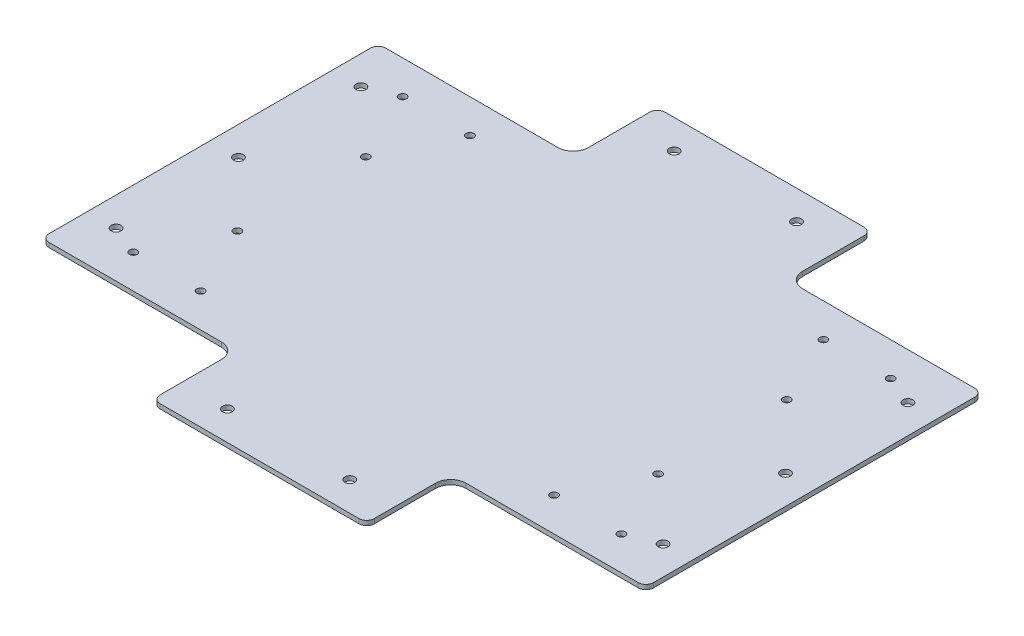
SolidWorks part; units mm, degrees
material "1060 Сплав"
ref_plane "Спереди" through (0, 0, 0) normal (0, 0, 1) x (1, 0, 0)
ref_plane "Сверху" through (0, 0, 0) normal (0, 1, 0) x (1, 0, 0)
ref_plane "Справа" through (0, 0, 0) normal (1, 0, 0) x (0, 0, -1)
sketch "Эскиз1" plane through (0, 0, 0) normal (0, 1, 0) x (1, 0, 0)
  line L1 (-65, -165) -> (65, -165)
  line L2 (-197.5, -105) -> (-197.5, 105)
  line L3 (-65, 165) -> (65, 165)
  line L4 (197.5, -105) -> (197.5, 105)
  line L5 (197.5, -105) -> (137.5, -105) construction
  line L6 (137.5, -110) -> (137.5, -66.2968) construction
  line L18 (-284.5497, 0) -> (284.3305, 0) construction
  line L19 (-160.9018, 110) -> (-134.9018, 110)
  line L39 (-70, 120) -> (-70, 160)
  line L40 (0, 262.7398) -> (0, -186.5795) construction
  line L41 (-192.5, 110) -> (-80, 110)
  line L43 (-192.5, -110) -> (-80, -110)
  line L44 (-70, -120) -> (-70, -160)
  line L45 (70, 120) -> (70, 160)
  line L46 (192.5, 110) -> (80, 110)
  line L47 (192.5, -110) -> (80, -110)
  line L48 (70, -120) -> (70, -160)
  line L54 (160.9018, -110) -> (134.9018, -110)
  line L60 (160.9018, 110) -> (134.9018, 110)
  line L65 (40, -146) -> (-40, -146) construction
  line L66 (-178.7687, -80) -> (-178.7687, 80) construction
  arc A0 (70, -120) -> (80, -110) centre (80, -120) cw
  arc A1 (70, 120) -> (80, 110) centre (80, 120) ccw
  arc A2 (-80, -110) -> (-70, -120) centre (-80, -120) cw
  arc A3 (-70, 120) -> (-80, 110) centre (-80, 120) cw
  arc A4 (192.5, -110) -> (197.5, -105) centre (192.5, -105) ccw
  arc A5 (70, -160) -> (65, -165) centre (65, -160) cw
  arc A6 (-70, -160) -> (-65, -165) centre (-65, -160) ccw
  arc A7 (-192.5, -110) -> (-197.5, -105) centre (-192.5, -105) cw
  arc A8 (-192.5, 110) -> (-197.5, 105) centre (-192.5, 105) ccw
  arc A9 (197.5, 105) -> (192.5, 110) centre (192.5, 105) ccw
  arc A10 (70, 160) -> (65, 165) centre (65, 160) ccw
  arc A11 (-70, 160) -> (-65, 165) centre (-65, 160) cw
  circle A12 centre (40, 146) radius 3.2
  circle A13 centre (40, -146) radius 3.2
  circle A14 centre (-40, -146) radius 3.2
  circle A15 centre (-40, 146) radius 3.2
  circle A16 centre (-178.7687, 80) radius 3.2
  circle A17 centre (-178.7687, -80) radius 3.2
  circle A18 centre (-178.7687, 0) radius 3.2
  circle A19 centre (178.7687, 80) radius 3.2
  circle A20 centre (178.7687, 0) radius 3.2
  circle A21 centre (178.7687, -80) radius 3.2
  circle A22 centre (137.5, -42) radius 2.5
  circle A23 centre (159.5, -88) radius 2.5
  circle A24 centre (115.5, -88) radius 2.5
  circle A25 centre (-159.5, -88) radius 2.5
  circle A26 centre (-137.5, -42) radius 2.5
  circle A27 centre (-115.5, -88) radius 2.5
  circle A28 centre (159.5, 88) radius 2.5
  circle A29 centre (137.5, 42) radius 2.5
  circle A30 centre (115.5, 88) radius 2.5
  circle A31 centre (-115.5, 88) radius 2.5
  circle A32 centre (-137.5, 42) radius 2.5
  circle A33 centre (-159.5, 88) radius 2.5
  point P0 (0, 0)
  point P3 (70, -110)
  point P17 (-147.9018, 110)
  point P18 (-147.9018, 110)
  point P46 (70, 110)
  point P52 (-70, -110)
  point P55 (-70, 110)
  point P56 (-147.9018, 0)
  point P59 (-178.7687, 0)
  point P62 (178.7687, 80)
  point P77 (197.5, -110)
  point P80 (70, -165)
  point P83 (-70, -165)
  point P86 (-197.5, -110)
  point P89 (-197.5, 110)
  point P92 (197.5, 110)
  point P95 (70, 165)
  point P98 (-70, 165)
  point P99 (178.7687, 0)
  point P100 (40, 146)
  point P101 (178.7687, -80)
  point P103 (-40, 146)
  dimension "D2" = 19
  dimension "D6" = 10
  dimension "D11" = 40
  dimension "D12" = 40
  dimension "D4" = 5
  dimension "D17" = 5
  dimension "D9" = 6.4
  dimension "D3" = 38
  dimension "D14" = 5
  dimension "D5" = 330
  dimension "D7" = 395
  dimension "D8" = 68
  dimension "D10" = 60
  dimension "D13" = 22
  dimension "D15" = 80
  dimension "D16" = 80
  dimension "D18" = 18.7313
  dimension "D19" = 19
extrude "Бобышка-Вытянуть1" add sketch "Эскиз1" along normal blind 3 separate body contours A11 L39 A3 L41 L43 A2 L44 A6 L1 A5 L48 A0 L47 L46 A1 L45 A10 L3 | L4 A9 L46 L47 A4 | L46 | L47 | L41 A8 L2 A7 L43 | L19 region at (0, 0, 0)
